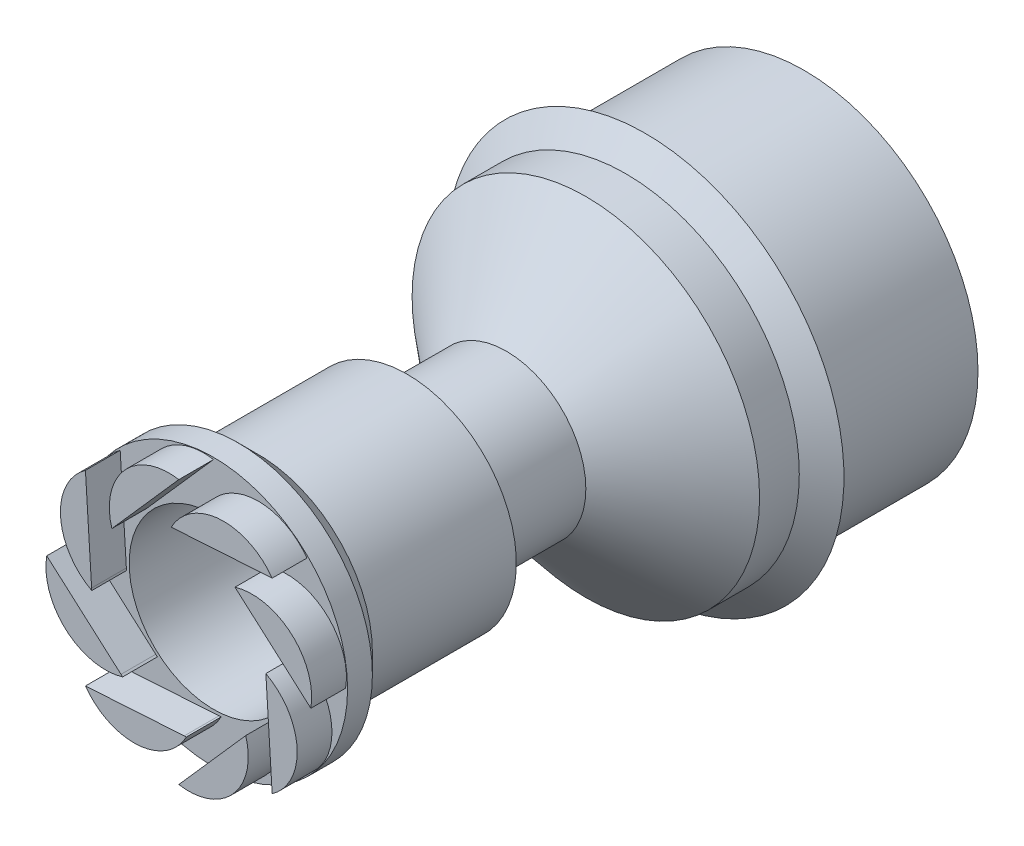
SolidWorks part; units mm, degrees
ref_plane "정면" through (0, 0, 0) normal (0, 0, 1) x (1, 0, 0)
ref_plane "윗면" through (0, 0, 0) normal (0, 1, 0) x (1, 0, 0)
ref_plane "우측면" through (0, 0, 0) normal (1, 0, 0) x (0, 0, -1)
sketch "스케치1" plane through (0, 0, 0) normal (0, 0, 1) x (1, 0, 0)
  circle A0 centre (0, 0) radius 1.75
  circle A1 centre (0, 0) radius 1.65
  dimension "D1" = 3.5
  dimension "D2" = 3.3
extrude "보스-돌출1" add sketch "스케치1" along normal blind 2.2
sketch "스케치2" plane through (0, 0, 0) normal (0, 1, 0) x (1, 0, 0)
  line L0 (1.75, -2.2) -> (1.75, -1.8)
  line L1 (1.75, -2.2) -> (1.75, 0) construction
  line L2 (1.75, -1.8) -> (2, -1.8)
  line L3 (2, -1.8) -> (2, -1.6)
  line L4 (2, -1.6) -> (1.75, -1.6)
  line L5 (1.75, -1.6) -> (1.75, -1.8)
  line L6 (2, -1.6) -> (1.75, -1.8)
  line L7 (0, 0) -> (0, -1.8769) construction
  dimension "D1" = 0.4
  dimension "D2" = 0.2
  dimension "D3" = 0.25
revolve "회전1" add sketch "스케치2" angle 360 about L7 region at (1.8333, 0, 1.6667)
sketch "스케치3" plane through (0, 0, 0) normal (0, 1, 0) x (1, 0, 0)
  line L0 (1.75, -2.2) -> (0.8, -2.2)
  line L1 (0.8, -2.2) -> (0.8, -3)
  line L2 (0.8, -3) -> (1.75, -2.2)
  line L3 (1.75, -2.2) -> (1.65, -2.2)
  line L4 (1.65, -2.2) -> (0.7, -3)
  line L5 (0.8, -3) -> (0.7, -3)
  line L6 (0, 0) -> (0, -3.1862) construction
  dimension "D1" = 0.8
  dimension "D2" = 0.95
  dimension "D3" = 0.1
revolve "회전2" add sketch "스케치3" angle 360 about L6 region at (1.2505, 0, 2.5793)
ref_plane "평면1" through (0, 0, 2.8) normal (0, 0, -1) x (-1, 0, 0)
sketch "스케치10" plane through (0, 0, 2.8) normal (0, 0, -1) x (-1, 0, 0)
  circle A0 centre (0, 0) radius 0.8
  circle A1 centre (0, 0) radius 0.7
  circle A2 centre (0, 0) radius 0.8 construction
  dimension "D1" = 0.1
extrude "보스-돌출2" add sketch "스케치10" along normal mid plane 2.4
sketch "스케치11" plane through (0, 0, 4) normal (0, 0, 1) x (1, 0, 0)
  circle A0 centre (0, 0) radius 0.7 construction
  circle A1 centre (0, 0) radius 0.8
  circle A2 centre (0, 0) radius 0.8
  circle A3 centre (0, 0) radius 0.7
  dimension "D1" = 0
extrude "보스-돌출4" add sketch "스케치11" along normal blind 0.9
sketch "스케치12" plane through (0, 0, 0) normal (0, 1, 0) x (1, 0, 0)
  line L0 (0.8, -4.9) -> (0.8, -4)
  line L2 (0.8, -4.9) -> (0, -4.9)
  line L3 (-0.8, -4.9) -> (0.8, -4.9) construction
  line L4 (0.8, -4.9) -> (1.1, -4.9)
  line L5 (1.1, -4.9) -> (1.1, -4)
  line L6 (1.1, -4) -> (0.8, -4)
  line L7 (0, 0) -> (0, -4.7) construction
  dimension "D1" = 0.9
  dimension "D2" = 0.3
revolve "회전3" add sketch "스케치12" angle 360 about L7 region at (0.95, 0, 4.45)
sketch "스케치13" plane through (0, 0, 4.9) normal (0, 0, 1) x (1, 0, 0)
  circle A0 centre (0, 0) radius 0.85
  circle A1 centre (0, 0) radius 0.7 construction
  dimension "D1" = 0.15
extrude "컷-돌출2" cut sketch "스케치13" against normal blind 0.5
chamfer "모따기1" distance 0.15 angle 60 1 edges at (0.7, 0, 4.4) first distance on face at (0.7, 0, 4.4)
sketch "스케치14" plane through (0, 0, 4.9) normal (0, 0, 1) x (1, 0, 0)
  circle A0 centre (0, 0) radius 0.85 construction
  circle A1 centre (0, 0) radius 1.1
  circle A2 centre (0, 0) radius 1.1
  circle A3 centre (0, 0) radius 0.85
  dimension "D1" = 0
extrude "보스-돌출5" add sketch "스케치14" along normal blind 0.6
sketch "스케치15" plane through (0, 0, 5.5) normal (0, 0, 1) x (1, 0, 0)
  circle A0 centre (0, 0) radius 1.35
  circle A1 centre (0, 0) radius 1.1 construction
  circle A2 centre (0, 0) radius 1.1
  dimension "D1" = 2.7
extrude "보스-돌출6" add sketch "스케치15" along normal blind 0.8 separate body
sketch "스케치17" plane through (0, 0, 5.5) normal (0, 0, 1) x (1, 0, 0)
  circle A0 centre (0, 0) radius 0.85 construction
  circle A1 centre (0, 0) radius 1.1
  circle A2 centre (0, 0) radius 1.1
  circle A3 centre (0, 0) radius 0.85
  dimension "D1" = 0
extrude "보스-돌출7" add sketch "스케치17" along normal blind 0.8
chamfer "모따기3" distance 0.2 angle 45 1 edges at (1.35, 0, 5.5)
sketch "스케치20" plane through (0, 0, 6.3) normal (0, 0, 1) x (1, 0, 0)
  line L0 (-0.6743, 0.5658) -> (0, 1.33)
  line L1 (-0.0767, 0.8769) -> (0.9405, 0.9405)
  line L2 (0.5658, 0.6743) -> (1.33, 0)
  line L3 (0.8769, 0.0767) -> (0.9405, -0.9405)
  line L4 (0.6743, -0.5658) -> (0, -1.33)
  line L5 (0.0767, -0.8769) -> (-0.9405, -0.9405)
  line L6 (-0.5658, -0.6743) -> (-1.33, 0)
  line L7 (-0.8769, -0.0767) -> (-0.9405, 0.9405)
  line L8 (0, 0) -> (0, 0.3485) construction
  line L9 (0, 0) -> (-0.2292, 0) construction
  line L10 (0.1558, -0.1308) -> (-0.1426, 0.1196) construction
  arc A1 (0, 1.33) -> (-0.6743, 0.5658) centre (-0.0997, 0.7383) ccw
  circle A2 centre (0, 0) radius 1.35 construction
  arc A3 (0.9405, 0.9405) -> (-0.0767, 0.8769) centre (0.4516, 0.5926) ccw
  arc A4 (1.33, 0) -> (0.5658, 0.6743) centre (0.7383, 0.0997) ccw
  arc A5 (0.9405, -0.9405) -> (0.8769, 0.0767) centre (0.5926, -0.4516) ccw
  arc A6 (0, -1.33) -> (0.6743, -0.5658) centre (0.0997, -0.7383) ccw
  arc A7 (-0.9405, -0.9405) -> (0.0767, -0.8769) centre (-0.4516, -0.5926) ccw
  arc A8 (-1.33, 0) -> (-0.5658, -0.6743) centre (-0.7383, -0.0997) ccw
  arc A9 (-0.9405, 0.9405) -> (-0.8769, -0.0767) centre (-0.5926, 0.4516) ccw
  circle A10 centre (0, 0) radius 0.7 construction
  circle A11 centre (0, 0) radius 1.35
  circle A12 centre (0, 0) radius 0.85 construction
  circle A13 centre (0, 0) radius 0.85
  circle A14 centre (0, 0) radius 0.7
  circle A15 centre (0, 0) radius 0.88
  point P29 (0, 0)
  circle M19 centre (0, 0) radius 0.85
  circle M20 centre (0, 0) radius 1.35
  dimension "D1" = 50
  dimension "D2" = 8
  dimension "D4" = 0.6
  dimension "D5" = 0.03
  dimension "D3" = 1.33
extrude "컷-돌출4" cut sketch "스케치20" against normal blind 0.35 contours A15 A5 L3 A6 L4 A7 L5 A8 L6 A9 L7 A1 L0 A3 L1 A4 L2 M20 | L3 A15 L2 L1 L0 L7 L6 L5 L4 M19 region at (-0.3758, 0.7681, 6.3) region at (-1.3118, 0, 6.3)
